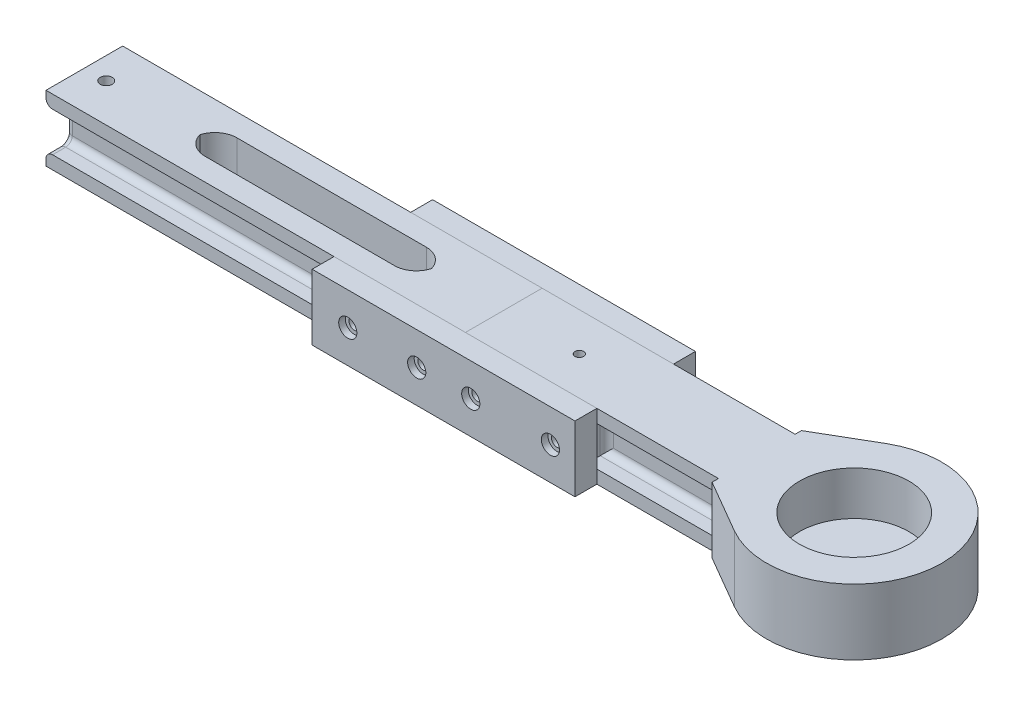
SolidWorks part; units mm, degrees
material "PLA "
ref_plane "Front Plane" through (0, 0, 0) normal (0, 0, 1) x (1, 0, 0)
ref_plane "Top Plane" through (0, 0, 0) normal (0, 1, 0) x (1, 0, 0)
ref_plane "Right Plane" through (0, 0, 0) normal (1, 0, 0) x (0, 0, -1)
sketch "Sketch1" plane through (0, 0, 0) normal (0, 1, 0) x (1, 0, 0)
  line L0 (0, 0) -> (-247, 0) construction
  line L1 (-247, 0) -> (-447, 0) construction
  dimension "D1" = 247
  dimension "D2" = 200
sketch "Sketch2" plane through (0, 0, 0) normal (0, 1, 0) x (1, 0, 0)
  line L1 (-247, -17.5) -> (0, -17.5)
  line L2 (-247, -17.5) -> (-247, 17.5)
  line L3 (-247, 17.5) -> (0, 17.5)
  line L4 (0, -17.5) -> (0, 17.5)
  point P4 (-247, 0)
  dimension "D1" = 35
extrude "Boss-Extrude1" add sketch "Sketch2" along normal blind 30 contours L1 L4 L3 L2
sketch "Sketch3" plane through (0, 0, 0) normal (0, -1, 0) x (1, 0, 0)
  line L0 (0, 0) -> (-21, 0) construction
  line L1 (0, 0) -> (-247, 0) construction
  circle A0 centre (-21, 0) radius 5.6
  dimension "D2" = 11.2
  dimension "D1" = 21
extrude "Cut-Extrude1" cut sketch "Sketch3" against normal through all
sketch "Sketch4" plane through (0, 30, 0) normal (0, 1, 0) x (1, 0, 0)
  line L0 (0, -17.5) -> (0, 17.5) construction
  line L1 (-14.9, 3.5218) -> (-21, 7.0437)
  line L2 (-21, 7.0437) -> (-27.1, 3.5218)
  line L3 (-27.1, 3.5218) -> (-27.1, -3.5218)
  line L4 (-27.1, -3.5218) -> (-21, -7.0437)
  line L5 (-21, -7.0437) -> (-14.9, -3.5218)
  line L6 (-14.9, -3.5218) -> (-14.9, 3.5218)
  line L7 (-27.1, 0) -> (-14.9, 0)
  circle A0 centre (-21, 0) radius 6.1 construction
  dimension "D1" = 12.2
extrude "Cut-Extrude2" cut sketch "Sketch4" against normal blind 22 contours L1 L2 L3 L4 L5 L6
sketch "Sketch5" plane through (0, 0, 0) normal (1, 0, 0) x (0, 0, -1)
  line L0 (0, 8) -> (0, 1) construction
  line L1 (-3.5218, 8) -> (3.5218, 8) construction
  line L2 (0, 1) -> (0, -2.0977) construction
  line L3 (2.5, 1) -> (2.5, -2.0977)
  line L4 (-2.5, 1) -> (-2.5, -2.0977)
  arc A0 (2.5, 1) -> (-2.5, 1) centre (0, 1) ccw
  arc A1 (-2.5, -2.0977) -> (2.5, -2.0977) centre (0, -2.0977) ccw
  point P5 (0, -0.5488)
  dimension "D1" = 7
  dimension "D2" = 5
sketch "Sketch6" plane through (0, 0, 0) normal (1, 0, 0) x (0, 0, -1)
  line L0 (0, 8) -> (0, 16) construction
  line L1 (-3.5218, 8) -> (3.5218, 8) construction
  line L2 (-17.5, 30) -> (17.5, 30) construction
  line L3 (-11.0435, 16) -> (11.453, 16)
  line L4 (-11.0435, 16) -> (-11.0435, 30)
  line L5 (-11.0435, 30) -> (11.453, 30)
  line L6 (11.453, 16) -> (11.453, 30)
  dimension "D1" = 8
extrude "Boss-Extrude3" add sketch "Sketch6" against normal blind 38
sketch "Sketch7" plane through (0, 0, 17.5) normal (0, 0, 1) x (1, 0, 0)
  line L0 (-21, 16) -> (-14.9, 16) construction
  line L1 (-27.1, 16) -> (-21, 16) construction
  line L2 (-27.1, 8) -> (-27.1, 16) construction
  line L3 (-14.9, 8) -> (-14.9, 16) construction
  line L4 (-15.4, 0) -> (-15.4, 8) construction
  line L5 (-26.6, 8) -> (-26.6, 0) construction
  line L6 (-21, 16) -> (-14.9, 16)
  line L7 (-27.1, 16) -> (-21, 16)
  line L8 (-27.1, 8) -> (-27.1, 16)
  line L9 (-14.9, 8) -> (-14.9, 16)
  line L10 (-15.4, 0) -> (-15.4, 8)
  line L11 (-26.6, 8) -> (-26.6, 0)
  line L12 (-27.1, 8) -> (-26.6, 8)
  line L13 (-15.4, 8) -> (-14.9, 8)
  line L14 (-26.6, 0) -> (-15.4, 0)
extrude "Cut-Extrude4" cut sketch "Sketch7" against normal up to vertex (17.5 mm away) up to point (-14.9, 30, 0)
sketch "Sketch9" plane through (0, 30, 0) normal (0, 1, 0) x (1, 0, 0)
  line L0 (-27.1, 3.5218) -> (-14.9, -3.5218) construction
  line L1 (-27.1, -3.5218) -> (-14.9, 3.5218) construction
  line L6 (-14.9, 3.5218) -> (-21, 7.0437)
  line L7 (-21, 7.0437) -> (-27.1, 3.5218)
  line L8 (-27.1, 3.5218) -> (-27.1, -3.5218)
  line L9 (-27.1, -3.5218) -> (-21, -7.0437)
  line L10 (-21, -7.0437) -> (-14.9, -3.5218)
  line L11 (-14.9, -3.5218) -> (-14.9, 3.5218)
  line L12 (-14.9, 3.5218) -> (-21, 7.0437) construction
  line L13 (-21, 7.0437) -> (-27.1, 3.5218) construction
  line L14 (-27.1, 3.5218) -> (-27.1, -3.5218) construction
  line L15 (-27.1, -3.5218) -> (-21, -7.0437) construction
  line L16 (-21, -7.0437) -> (-14.9, -3.5218) construction
  line L17 (-14.9, -3.5218) -> (-14.9, 3.5218) construction
  circle A0 centre (-21, 0) radius 2
  dimension "D2" = 4
  dimension "D1" = 0
extrude "Cut-Extrude5" cut sketch "Sketch9" against normal blind 38
sketch "Sketch15" plane through (0, 30, 0) normal (0, 1, 0) x (1, 0, 0)
  line L0 (-247, 0) -> (-237, 0) construction
  line L1 (0, 0) -> (-247, 0) construction
  circle A0 centre (-237, 0) radius 2.75
  dimension "D2" = 5.5
  dimension "D1" = 10
extrude "Cut-Extrude10" cut sketch "Sketch15" against normal blind 9
sketch "Sketch16" plane through (0, 0, 0) normal (0, -1, 0) x (1, 0, 0)
  line L1 (-241.1302, 2.6504) -> (-241.3604, -2.2517)
  line L2 (-241.3604, -2.2517) -> (-237.2302, -4.9021)
  line L3 (-237.2302, -4.9021) -> (-232.8698, -2.6504)
  line L4 (-232.8698, -2.6504) -> (-232.6396, 2.2517)
  line L5 (-232.6396, 2.2517) -> (-236.7698, 4.9021)
  line L6 (-236.7698, 4.9021) -> (-241.1302, 2.6504)
  circle A0 centre (-237, 0) radius 2.75 construction
  circle A1 centre (-237, 0) radius 2.75 construction
  circle A2 centre (-237, 0) radius 4.25 construction
  dimension "D1" = 8.5
extrude "Cut-Extrude11" cut sketch "Sketch16" against normal up to surface (21 mm away) up to face at (-237, 21, 2.75)
sketch "Sketch17" plane through (0, 30, 0) normal (0, 1, 0) x (1, 0, 0)
  line L0 (0, 0) -> (-247, 0) construction
  line L2 (-58.6673, -9.5384) -> (-188.3327, -9.5384)
  line L3 (-58.6673, -9.5384) -> (-58.6673, 9.5384)
  line L4 (-58.6673, 9.5384) -> (-188.3327, 9.5384)
  line L5 (-188.3327, -9.5384) -> (-188.3327, 9.5384)
  line L6 (-58.6673, -9.5384) -> (-188.3327, 9.5384) construction
  line L7 (-58.6673, 9.5384) -> (-188.3327, -9.5384) construction
  point P4 (-123.5, 0)
extrude "Cut-Extrude12" [suppressed] cut sketch "Sketch17" against normal through all
fillet "Fillet1" [suppressed] radius 10
sketch "Sketch19" plane through (0, 0, 0) normal (1, 0, 0) x (0, 0, -1)
  line L5 (17.5, 0) -> (17.5, 30)
  line L6 (17.5, 30) -> (-17.5, 30)
  line L7 (-17.5, 30) -> (-17.5, 0)
  line L8 (-17.5, 0) -> (17.5, 0)
  line L9 (17.5, 0) -> (17.5, 30)
  line L10 (17.5, 30) -> (-17.5, 30)
  line L11 (-17.5, 30) -> (-17.5, 0)
  line L12 (-17.5, 0) -> (17.5, 0)
  dimension "D1" = 0
extrude "Boss-Extrude5" add sketch "Sketch19" along normal blind 55
sketch "Sketch18" plane through (0, 30, 0) normal (0, 1, 0) x (1, 0, 0)
  line L0 (84.4055, -34.5857) -> (84.4055, 34.5857) construction
  line L1 (55, 17.5) -> (55, -17.5)
  line L2 (55, -17.5) -> (84.4055, -34.5857)
  line L5 (84.4055, 34.5857) -> (55, 17.5)
  line L6 (55, 0) -> (84.4055, 0) construction
  arc A1 (84.4055, -34.5857) -> (84.4055, 34.5857) centre (104.5011, 0) ccw
  point P7 (144.5011, 0)
  dimension "D1" = 40
extrude "Boss-Extrude4" add sketch "Sketch18" against normal up to vertex (30 mm away)
sketch "Sketch20" plane through (0, 0, 0) normal (0, -1, 0) x (1, 0, 0)
  circle A0 centre (104.5011, 0) radius 25
  dimension "D1" = 50
sketch "Sketch21" plane through (0, 30, 0) normal (0, 1, 0) x (1, 0, 0)
  circle A1 centre (104.5011, 0) radius 25
  circle A2 centre (104.5011, 0) radius 25
  dimension "D1" = 0
extrude "Cut-Extrude14" cut sketch "Sketch21" against normal blind 20
sketch "Sketch22" plane through (0, 0, 0) normal (0, -1, 0) x (1, 0, 0)
  line L0 (-247, 0) -> (144.5011, 0) construction
  arc A0 (84.4055, -34.5857) -> (84.4055, 34.5857) centre (104.5011, 0) ccw construction
  point P6 (-21, 0)
sketch "Sketch23" plane through (0, 0, 17.5) normal (0, 0, 1) x (1, 0, 0)
  line L0 (-55.4989, 91.556) -> (-55.4989, -31.556)
  line L3 (144.5011, 0) -> (144.5011, 64.4466) construction
  line L4 (-27.1, 16) -> (-27.1, 55.3644) construction
  point P3 (-55.4989, 30)
  dimension "D1" = 200
split "Split1" trim tools "Sketch23" bodies to split 118 resulting bodies 119 120
sketch "Sketch24" plane through (0, 0, 17.5) normal (0, 0, 1) x (1, 0, 0)
  line L0 (-55.4989, 30) -> (-55.4989, 0) construction
  line L1 (0, 0) -> (-247, 0) construction
  line L2 (-55.4989, 91.556) -> (-55.4989, -31.556) construction
  line L3 (-55.4989, 0) -> (-55.4989, 15) construction
  line L4 (-55.4989, 30) -> (55, 30) construction
  line L5 (-115.4989, 0) -> (4.5011, 0)
  line L6 (-115.4989, 0) -> (-115.4989, 30)
  line L7 (-115.4989, 30) -> (4.5011, 30)
  line L8 (4.5011, 0) -> (4.5011, 30)
  line L9 (-115.4989, 0) -> (4.5011, 30) construction
  line L10 (-115.4989, 30) -> (4.5011, 0) construction
  dimension "D1" = 120
extrude "Boss-Extrude6" add sketch "Sketch24" along normal blind 10 separate body contours L6 L7 L8 L5
sketch "Sketch26" plane through (0, 0, -17.5) normal (0, 0, -1) x (-1, 0, 0)
  line L4 (-4.5011, 0) -> (115.4989, 0)
  line L5 (-4.5011, 30) -> (-4.5011, 0)
  line L6 (115.4989, 30) -> (-4.5011, 30)
  line L7 (115.4989, 0) -> (115.4989, 30)
  line L8 (-4.5011, 0) -> (115.4989, 0)
  line L9 (-4.5011, 30) -> (-4.5011, 0)
  line L10 (115.4989, 30) -> (-4.5011, 30)
  line L11 (115.4989, 0) -> (115.4989, 30)
  dimension "D1" = 0
extrude "Boss-Extrude7" add sketch "Sketch26" along normal blind 10 separate body
sketch "Sketch27" plane through (0, 0, -27.5) normal (0, 0, -1) x (-1, 0, 0)
  line L0 (-4.5011, 15) -> (115.4989, 15) construction
  line L1 (-4.5011, 30) -> (-4.5011, 0) construction
  line L2 (115.4989, 0) -> (115.4989, 30) construction
  circle A0 centre (43.074, 15) radius 2.5
  circle A1 centre (67.7461, 15) radius 2.5
  circle A2 centre (99.2164, 15) radius 2.5
  circle A3 centre (6.7066, 15) radius 2.5
  dimension "D1" = 5
extrude "Cut-Extrude15" cut sketch "Sketch27" against normal through all
sketch "Sketch31" plane through (0, 0, -27.5) normal (0, 0, -1) x (-1, 0, 0)
  line L1 (45.4412, 10.9) -> (47.8083, 15)
  line L2 (47.8083, 15) -> (45.4412, 19.1)
  line L3 (45.4412, 19.1) -> (40.7069, 19.1)
  line L4 (40.7069, 19.1) -> (38.3397, 15)
  line L5 (38.3397, 15) -> (40.7069, 10.9)
  line L6 (40.7069, 10.9) -> (45.4412, 10.9)
  line L7 (70.1133, 10.9) -> (72.4804, 15)
  line L8 (72.4804, 15) -> (70.1133, 19.1)
  line L9 (70.1133, 19.1) -> (65.379, 19.1)
  line L10 (65.379, 19.1) -> (63.0119, 15)
  line L11 (63.0119, 15) -> (65.379, 10.9)
  line L12 (65.379, 10.9) -> (70.1133, 10.9)
  line L13 (9.0737, 10.9) -> (11.4408, 15)
  line L14 (11.4408, 15) -> (9.0737, 19.1)
  line L15 (9.0737, 19.1) -> (4.3394, 19.1)
  line L16 (4.3394, 19.1) -> (1.9723, 15)
  line L17 (1.9723, 15) -> (4.3394, 10.9)
  line L18 (4.3394, 10.9) -> (9.0737, 10.9)
  line L19 (101.5835, 10.9) -> (103.9507, 15)
  line L20 (103.9507, 15) -> (101.5835, 19.1)
  line L21 (101.5835, 19.1) -> (96.8493, 19.1)
  line L22 (96.8493, 19.1) -> (94.4821, 15)
  line L23 (94.4821, 15) -> (96.8493, 10.9)
  line L24 (96.8493, 10.9) -> (101.5835, 10.9)
  circle A0 centre (43.074, 15) radius 4.1 construction
  circle A1 centre (67.7461, 15) radius 4.1 construction
  circle A2 centre (6.7066, 15) radius 4.1 construction
  circle A3 centre (99.2164, 15) radius 4.1 construction
  dimension "D1" = 8.2
extrude "Cut-Extrude17" cut sketch "Sketch31" against normal blind 3
sketch "Sketch32" plane through (0, 0, 27.5) normal (0, 0, 1) x (1, 0, 0)
  circle A0 centre (-67.7461, 15) radius 4.15
  circle A1 centre (-43.074, 15) radius 4.15
  circle A2 centre (-99.2164, 15) radius 4.15
  circle A3 centre (-6.7066, 15) radius 4.15
  dimension "D1" = 8.3
extrude "Cut-Extrude18" cut sketch "Sketch32" against normal blind 3
sketch "Sketch28" plane through (-247, 0, 0) normal (-1, 0, 0) x (0, 0, 1)
  line L1 (-17.5, 30) -> (17.5, 30)
  line L2 (-17.5, 30) -> (-17.5, 36.9638)
  line L3 (-17.5, 36.9638) -> (17.5, 36.9638)
  line L4 (17.5, 30) -> (17.5, 36.9638)
extrude "Boss-Extrude8" [suppressed] add sketch "Sketch28" against normal blind 40
sketch "Sketch30" plane through (0, 21, 0) normal (0, -1, 0) x (1, 0, 0)
  circle A0 centre (-237, 0) radius 2.75 construction
  circle A1 centre (-237, 0) radius 2.75
sketch "Sketch33" plane through (-247, 0, 0) normal (-1, 0, 0) x (0, 0, 1)
  line L0 (-17.5, 30) -> (-17.5, 24)
  line L1 (-17.5, 30) -> (-17.5, 0) construction
  line L2 (-17.5, 24) -> (17.5, 24) construction
  line L3 (17.5, 30) -> (17.5, 0) construction
  line L4 (-17.5, 6) -> (17.5, 6) construction
  line L5 (0, 24) -> (0, 6) construction
  line L6 (17.5, 0) -> (17.5, 30) construction
  line L7 (17.5, 0) -> (-17.5, 0) construction
  line L8 (17.5, 30) -> (-17.5, 30) construction
  line L9 (-8.5, 24) -> (-8.5, 6)
  line L10 (8.5, 24) -> (8.5, 6)
  line L11 (-8.5, 15) -> (8.5, 15) construction
  line L12 (-17.5, 24) -> (-8.5, 24)
  line L13 (-8.5, 6) -> (-17.5, 6)
  line L14 (-17.5, 6) -> (-17.5, 0)
  line L15 (-17.5, 0) -> (-17.5, 30) construction
  line L16 (-17.5, 0) -> (17.5, 0)
  line L17 (27.5, 0) -> (17.5, 0) construction
  line L18 (17.5, 0) -> (17.5, 6)
  line L19 (17.5, 6) -> (8.5, 6)
  line L20 (8.5, 24) -> (17.5, 24)
  line L21 (17.5, 24) -> (17.5, 30)
  line L22 (17.5, 30) -> (-17.5, 30)
  line L24 (-24.3906, 37.0172) -> (24.3906, 37.0172)
  line L25 (-24.3906, 37.0172) -> (-24.3906, -7.0172)
  line L26 (-24.3906, -7.0172) -> (24.3906, -7.0172)
  line L27 (24.3906, 37.0172) -> (24.3906, -7.0172)
  line L28 (-24.3906, 37.0172) -> (24.3906, -7.0172) construction
  line L29 (-24.3906, -7.0172) -> (24.3906, 37.0172) construction
  point P9 (0, 24)
  point P12 (0, 6)
  point P24 (0, 15)
  point P25 (0, 15)
  dimension "D1" = 6
  dimension "D2" = 6
  dimension "D3" = 17
extrude "Cut-Extrude19" cut sketch "Sketch33" against normal blind 133 contours L24 L27 L26 L25
sketch "Sketch34" plane through (0, 0, 0) normal (1, 0, 0) x (0, 0, -1)
  line L4 (24.3906, 37.0172) -> (-24.3906, 37.0172)
  line L5 (-24.3906, 37.0172) -> (-24.3906, -7.0172)
  line L6 (-24.3906, -7.0172) -> (24.3906, -7.0172)
  line L7 (24.3906, -7.0172) -> (24.3906, 37.0172)
  line L8 (24.3906, 37.0172) -> (-24.3906, 37.0172)
  line L9 (-24.3906, 37.0172) -> (-24.3906, -7.0172)
  line L10 (-24.3906, -7.0172) -> (24.3906, -7.0172)
  line L11 (24.3906, -7.0172) -> (24.3906, 37.0172)
  line L20 (-17.5, 30) -> (-17.5, 24)
  line L21 (-17.5, 24) -> (-8.5, 24)
  line L22 (-8.5, 24) -> (-8.5, 6)
  line L23 (-8.5, 6) -> (-17.5, 6)
  line L24 (-17.5, 6) -> (-17.5, 0)
  line L25 (-17.5, 0) -> (17.5, 0)
  line L26 (17.5, 0) -> (17.5, 6)
  line L27 (17.5, 6) -> (8.5, 6)
  line L28 (8.5, 6) -> (8.5, 24)
  line L29 (8.5, 24) -> (17.5, 24)
  line L30 (17.5, 24) -> (17.5, 30)
  line L31 (17.5, 30) -> (-17.5, 30)
  line L32 (-17.5, 30) -> (-17.5, 24)
  line L33 (-17.5, 24) -> (-8.5, 24)
  line L34 (-8.5, 24) -> (-8.5, 6)
  line L35 (-8.5, 6) -> (-17.5, 6)
  line L36 (-17.5, 6) -> (-17.5, 0)
  line L37 (-17.5, 0) -> (17.5, 0)
  line L38 (17.5, 0) -> (17.5, 6)
  line L39 (17.5, 6) -> (8.5, 6)
  line L40 (8.5, 6) -> (8.5, 24)
  line L41 (8.5, 24) -> (17.5, 24)
  line L42 (17.5, 24) -> (17.5, 30)
  line L43 (17.5, 30) -> (-17.5, 30)
  dimension "D1" = 0
  dimension "D2" = 0
extrude "Cut-Extrude20" cut sketch "Sketch34" along normal blind 60
fillet "Fillet3" radius 3 12 edges at (-247, 24, 13) (-247, 6, 13) (-247, 6, -13) (-247, 24, -13) (-180.5, 24, 8.5) (-114, 15, 8.5) (-180.5, 6, 8.5) (-247, 15, 8.5) (-180.5, 6, -8.5) (-114, 15, -8.5) (-180.5, 24, -8.5) (-247, 15, -8.5)
fillet "Fillet4" radius 3 8 edges at (60, 15, 8.5) (30, 24, 8.5) (0, 15, 8.5) (30, 6, 8.5) (60, 15, -8.5) (30, 6, -8.5) (0, 15, -8.5) (30, 24, -8.5)
other "Save Bodies1"
sketch "Sketch29" plane through (0, 30, 0) normal (0, 1, 0) x (1, 0, 0)
  line L0 (-88.1262, 0) -> (-194.6695, 0) construction
  line L1 (0, 0) -> (-247, 0) construction
  line L2 (-88.1262, -7.2908) -> (-88.1262, 7.2908)
  line L3 (-88.1262, -7.2908) -> (-194.6695, -7.2908)
  line L4 (-194.6695, -7.2908) -> (-194.6695, 7.2908)
  line L5 (-194.6695, 7.2908) -> (-88.1262, 7.2908)
  point P7 (-88.1262, 0)
extrude "Cut-Extrude16" cut sketch "Sketch29" against normal through all
fillet "Fillet2" radius 10 4 edges at (-194.6695, 15, 7.2908) (-194.6695, 15, -7.2908) (-88.1262, 15, 7.2908) (-88.1262, 15, -7.2908)
other "Save Bodies2"
other "Save Bodies3"
equation "\"2.5c\"=10"
